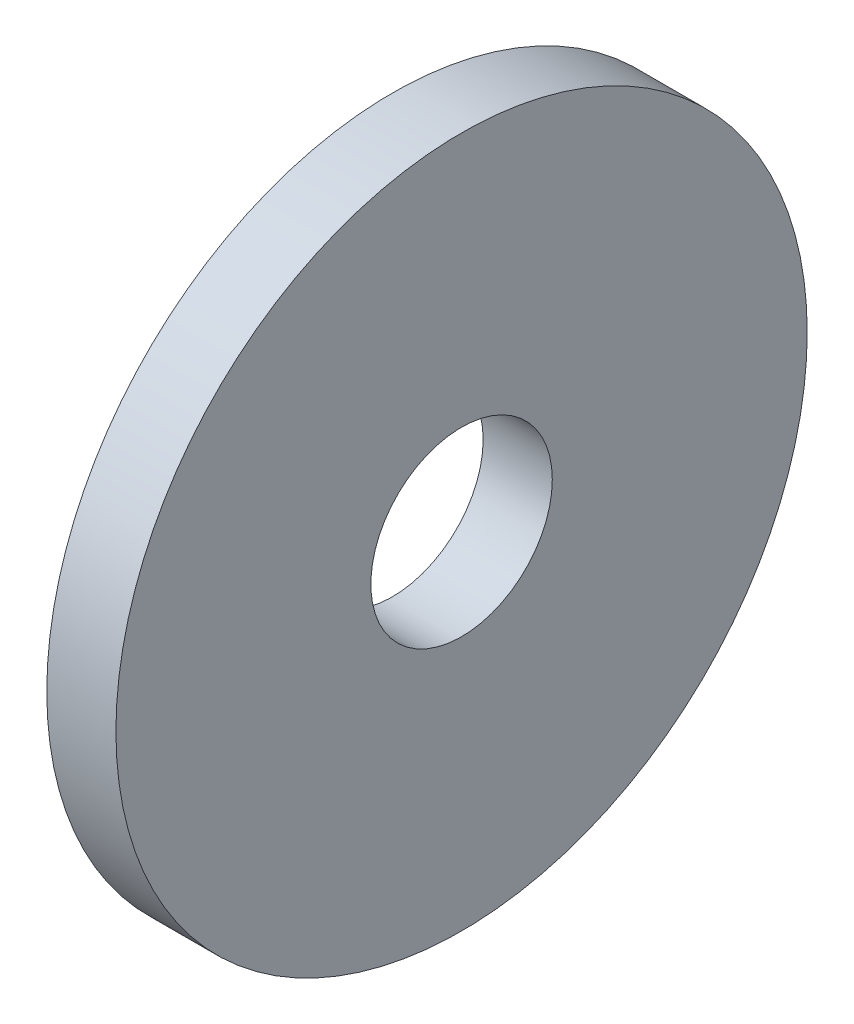
SolidWorks part; units mm, degrees
ref_plane "Спереди" through (0, 0, 0) normal (0, 0, 1) x (1, 0, 0)
ref_plane "Сверху" through (0, 0, 0) normal (0, 1, 0) x (1, 0, 0)
ref_plane "Справа" through (0, 0, 0) normal (1, 0, 0) x (0, 0, -1)
sketch "Эскиз1" plane through (0, 0, 0) normal (1, 0, 0) x (0, 0, -1)
  circle A0 centre (0, 0) radius 5.25
  circle A1 centre (0, 0) radius 20
  dimension "D1" = 10.5
  dimension "D2" = 40
base flange "Базовая кромка1" sketch "Эскиз1" thickness 4 reverse thickness direction no parameters "D1"=1.5
sketch "Сгиб-Линии1" [suppressed] plane through (0, 0, 0) normal (0, 1, 0) x (1, 0, 0)
sketch "Граничная рамка1" [suppressed] plane through (0, 0, 0) normal (0, 1, 0) x (1, 0, 0)
sheet metal parameters "Листовой металл3" thickness 4 parameters "D1"=1.5
flat pattern "Развертка3" [suppressed]
sketch "Сгиб-Линии2" plane through (0, 0, 0) normal (0, 1, 0) x (1, 0, 0)
sketch3d "Граничная рамка2" [suppressed]
  line L0 (19.9818, 20.0182, 0) -> (20.0182, -19.9818, 0) construction
  line L1 (-20.0181, 19.9818, 0) -> (-19.9817, -20.0182, 0) construction
  line L2 (19.9818, 20.0182, 0) -> (-20.0181, 19.9818, 0) construction
  line L3 (20.0182, -19.9818, 0) -> (-19.9817, -20.0182, 0) construction
